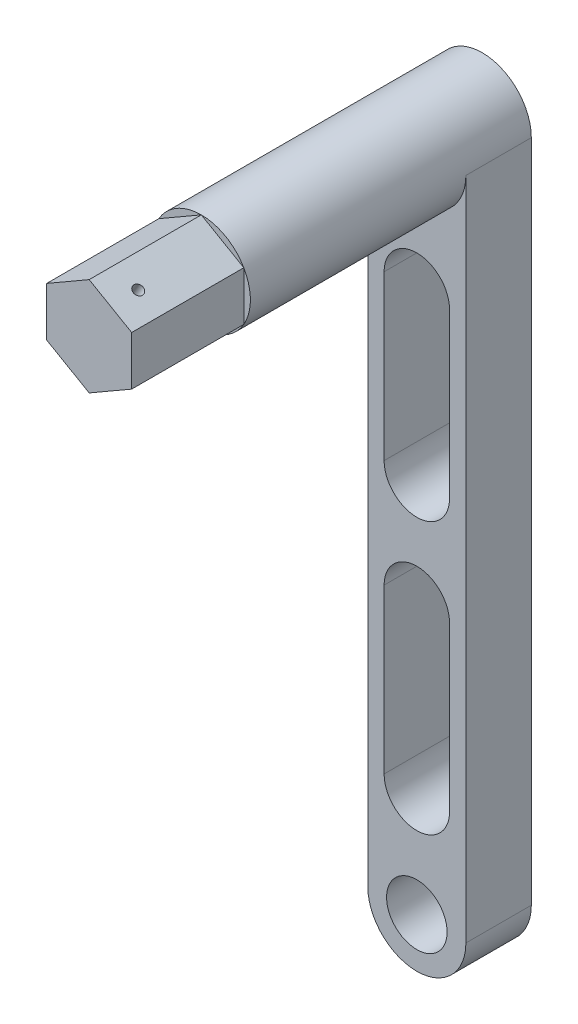
SolidWorks part; units mm, degrees
material "PEI"
ref_plane "Front Plane" through (0, 0, 0) normal (0, 0, 1) x (1, 0, 0)
ref_plane "Top Plane" through (0, 0, 0) normal (0, 1, 0) x (1, 0, 0)
ref_plane "Right Plane" through (0, 0, 0) normal (1, 0, 0) x (0, 0, -1)
sketch "Sketch1" plane through (0, 0, 0) normal (0, 0, 1) x (1, 0, 0)
  line L0 (0, -50.8) -> (0, 50.8) construction
  line L1 (-7.5, -50.8) -> (-7.5, 50.8)
  line L2 (7.5, -50.8) -> (7.5, 50.8)
  line L3 (0, -34.675) -> (0, -9.675) construction
  line L4 (-5, -34.675) -> (-5, -9.675)
  line L5 (5, -34.675) -> (5, -9.675)
  line L6 (0, 31.8) -> (0, 6.8) construction
  line L7 (5, 31.8) -> (5, 6.8)
  line L8 (-5, 31.8) -> (-5, 6.8)
  line L9 (-5, 19.3) -> (5, 19.3) construction
  line L10 (-5, -22.175) -> (5, -22.175) construction
  line L12 (0, 58.3) -> (0, 36.8) construction
  arc A0 (-7.5, -50.8) -> (7.5, -50.8) centre (0, -50.8) ccw
  arc A1 (7.5, 50.8) -> (-7.5, 50.8) centre (0, 50.8) ccw
  circle A2 centre (0, -50.8) radius 4.625
  arc A4 (-5, -34.675) -> (5, -34.675) centre (0, -34.675) ccw
  arc A5 (5, -9.675) -> (-5, -9.675) centre (0, -9.675) ccw
  arc A6 (5, 31.8) -> (-5, 31.8) centre (0, 31.8) ccw
  arc A7 (-5, 6.8) -> (5, 6.8) centre (0, 6.8) ccw
  circle A8 centre (0, 50.8) radius 7.5
  point P2 (0, 0)
  point P14 (0, -22.175)
  point P19 (0, 19.3)
  point P30 (0, -4.675)
  point P32 (0, -46.175)
  point P33 (0, -39.675)
  point P35 (0, 1.8)
  point P37 (0, 43.3)
  dimension "D3" = 9.25
  dimension "D1" = 101.6
  dimension "D2" = 15
  dimension "D4" = 10
  dimension "D5" = 6.5
  dimension "20" = 25
  dimension "D6" = 6.5
extrude "Boss-Extrude1" add sketch "Sketch1" along normal blind 10 contours A8 L1 A0 L2 A7 L8 A6 L7 A5 L5 A4 L4 A2 region at (-6.3987, 0, 0)
extrude "Boss-Extrude2" add sketch "Sketch1<4>" along normal blind 42.94 contours A1 A8 region at (0, 50.8, 0)
sketch "Sketch1<4>" plane through (0, 0, 0) normal (0, 0, 1) x (1, 0, 0) same geometry as "Sketch1"
sketch "Sketch2" plane through (0, 0, 42.94) normal (0, 0, 1) x (1, 0, 0)
  point P0 (0, 50.8)
sketch "Sketch3" plane through (0, 0, 42.94) normal (0, 0, 1) x (1, 0, 0)
  line L1 (0, 43.3) -> (6.4952, 47.05)
  line L2 (6.4952, 47.05) -> (6.4952, 54.55)
  line L3 (6.4952, 54.55) -> (0, 58.3)
  line L4 (0, 58.3) -> (-6.4952, 54.55)
  line L5 (-6.4952, 54.55) -> (-6.4952, 47.05)
  line L6 (-6.4952, 47.05) -> (0, 43.3)
  circle A0 centre (0, 50.8) radius 6.4952 construction
extrude "Boss-Extrude3" add sketch "Sketch3" along normal blind 17.14
sketch "Sketch4" plane through (25.2446, 43.725, 0) normal (0.5, 0.866, 0) x (0.866, -0.5, 0)
  line L0 (-25.4, -60.08) -> (-25.4, -55.08) construction
  line L1 (-21.65, -60.08) -> (-29.15, -60.08) construction
  circle A0 centre (-25.4, -55.83) radius 0.75
  point P6 (-25.4, -56.732)
  point P7 (-25.4, -55.83)
  dimension "D2" = 1.5
  dimension "D1" = 5
extrude "Cut-Extrude1" cut sketch "Sketch4" against normal through all both and the other way through all
